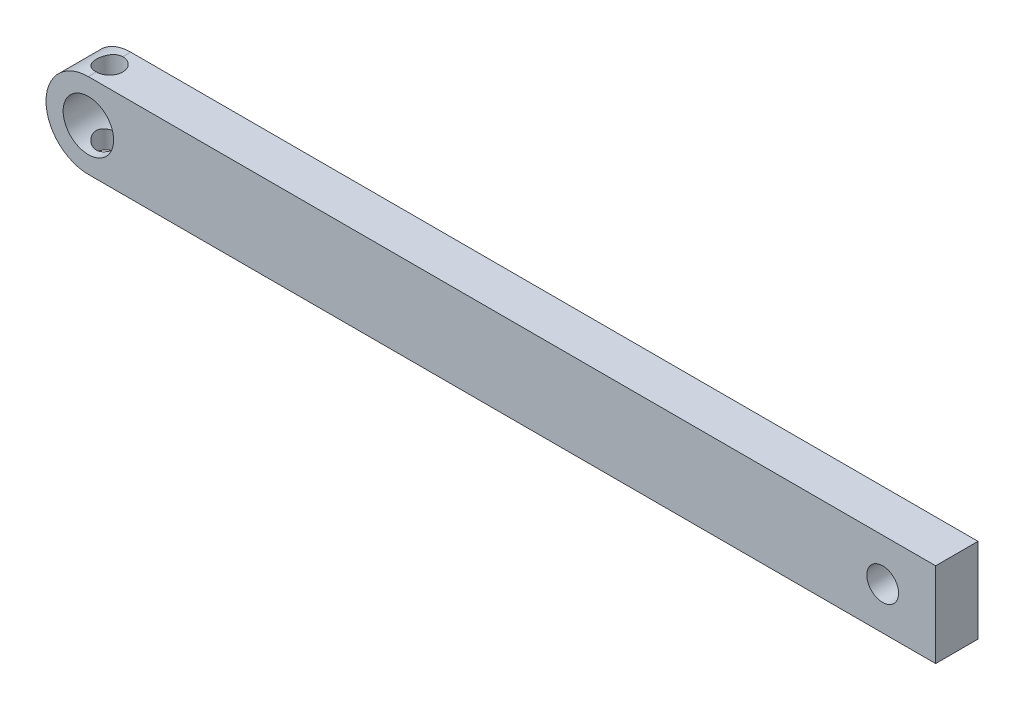
SolidWorks part; units mm, degrees
material "Plain Carbon Steel"
ref_plane "Front Plane" through (0, 0, 0) normal (0, 0, 1) x (1, 0, 0)
ref_plane "Top Plane" through (0, 0, 0) normal (0, 1, 0) x (1, 0, 0)
ref_plane "Right Plane" through (0, 0, 0) normal (1, 0, 0) x (0, 0, -1)
sketch "Sketch1" plane through (0, 0, 0) normal (0, 0, 1) x (1, 0, 0)
  line L0 (0, -8) -> (160, -8)
  line L1 (160, -8) -> (160, 8)
  line L2 (160, 8) -> (0, 8)
  arc A0 (0, 8) -> (0, -8) centre (0, 0) ccw
  dimension "D1" = 160
extrude "Boss-Extrude1" add sketch "Sketch1" along normal blind 8
sketch "Sketch2" plane through (0, 0, 0) normal (0, 0, 1) x (1, 0, 0)
  circle A0 centre (0, 0) radius 4.7625
  circle A1 centre (150, 0) radius 3
  dimension "D1" = 9.525
  dimension "D2" = 6
extrude "Cut-Extrude1" cut sketch "Sketch2" against normal mid plane 40
sketch "Sketch3" plane through (0, 0, 0) normal (0, 0, 1) x (1, 0, 0)
  circle A0 centre (30, 0) radius 4
  dimension "D1" = 8
extrude "Cut-Extrude2" cut sketch "Sketch3" against normal mid plane 1
sketch "Sketch4" plane through (0, 0, 0) normal (0, 1, 0) x (1, 0, 0)
  line L0 (0, -8) -> (0, 0) construction
  circle A0 centre (0, -4) radius 2.5
  dimension "D1" = 5
extrude "Cut-Extrude3" cut sketch "Sketch4" against normal mid plane 40
